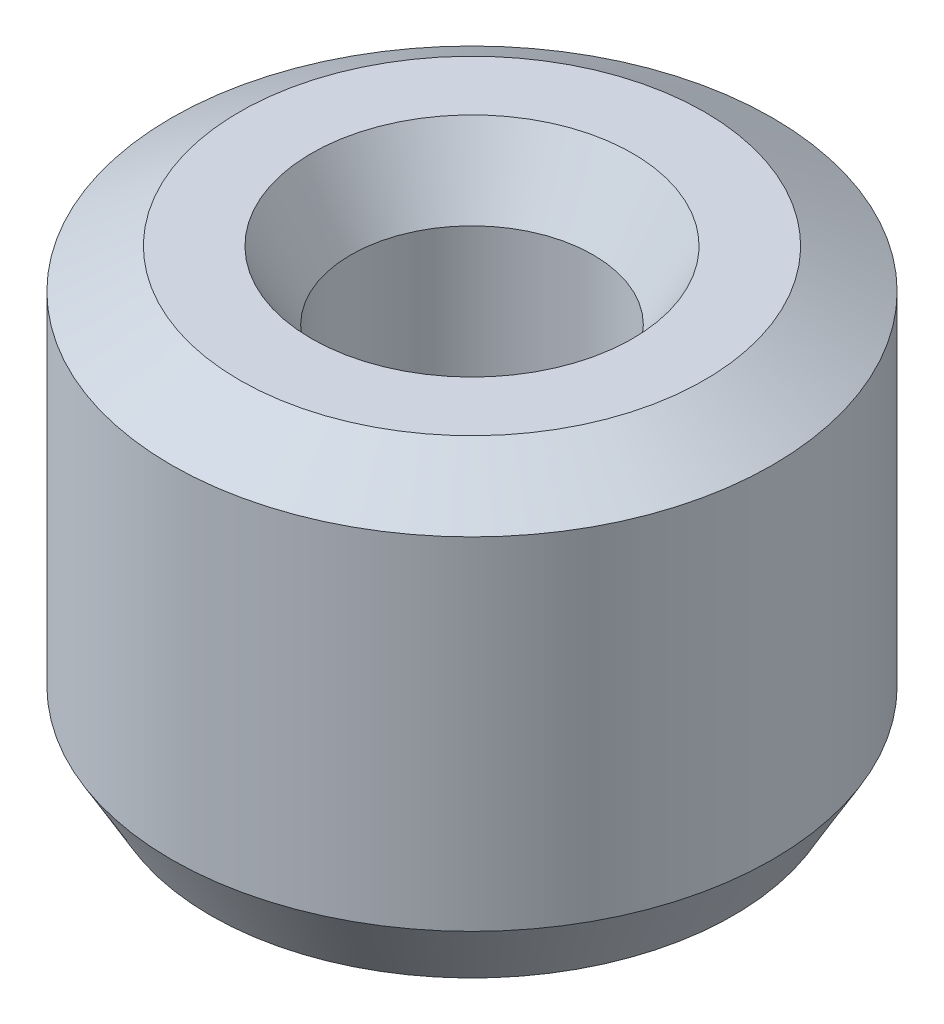
SolidWorks part; units mm, degrees
ref_plane "Front Plane" through (0, 0, 0) normal (0, 0, 1) x (1, 0, 0)
ref_plane "Top Plane" through (0, 0, 0) normal (0, 1, 0) x (1, 0, 0)
ref_plane "Right Plane" through (0, 0, 0) normal (1, 0, 0) x (0, 0, -1)
sketch "Sketch1" plane through (0, 0, 0) normal (0, 1, 0) x (1, 0, 0)
  circle A0 centre (0, 0) radius 17.5
  dimension "SLEEVE_OD" = 35
extrude "Boss-Extrude1" add sketch "Sketch1" along normal blind 26.1526
sketch "Sketch2" plane through (0, 0, 0) normal (0, 1, 0) x (1, 0, 0)
  circle A0 centre (0, 0) radius 7.0537
  dimension "BORE_D" = 14.1074
extrude "Cut-Extrude1" cut sketch "Sketch2" along normal through all
chamfer "Chamfer1" distance 2.2932 angle 60 4 edges at (0, 26.1526, 7.0537) (0, 0, 7.0537) (0, 0, 17.5) (0, 26.1526, 17.5) first distance on face at (0, 26.1526, 7.0537) first distance on face at (0, 0, 7.0537) first distance on face at (0, 26.1526, 17.5)
